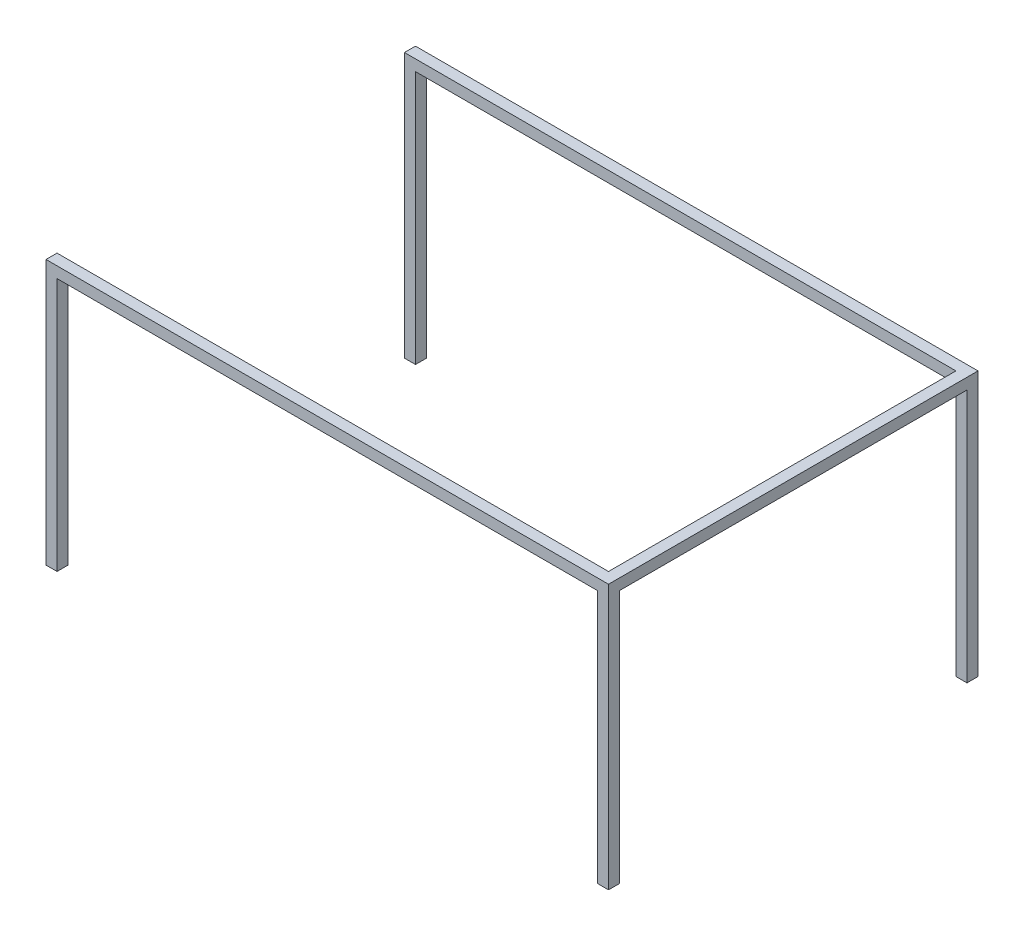
SolidWorks part; units mm, degrees
ref_plane "Front Plane" through (0, 0, 0) normal (0, 0, 1) x (1, 0, 0)
ref_plane "Top Plane" through (0, 0, 0) normal (0, 1, 0) x (1, 0, 0)
ref_plane "Right Plane" through (0, 0, 0) normal (1, 0, 0) x (0, 0, -1)
sketch "Sketch1" plane through (0, 0, 0) normal (0, 1, 0) x (1, 0, 0)
  line L0 (-55, 0) -> (55, 0) construction
  line L1 (-749.3, 400.05) -> (749.3, 400.05) construction
  line L2 (-749.3, 400.05) -> (-749.3, -400.05) construction
  line L3 (-749.3, -400.05) -> (749.3, -400.05) construction
  line L4 (749.3, 400.05) -> (749.3, -400.05) construction
  line L5 (-749.3, 400.05) -> (749.3, -400.05) construction
  line L6 (-749.3, -400.05) -> (749.3, 400.05) construction
  line L7 (749.3, -400.05) -> (-520.7, -400.05)
  line L8 (749.3, -400.05) -> (749.3, -425.45)
  line L9 (749.3, -425.45) -> (-520.7, -425.45)
  line L10 (-520.7, -400.05) -> (-520.7, -425.45)
  line L11 (749.3, 425.45) -> (-520.7, 425.45)
  line L12 (-520.7, 400.05) -> (-520.7, 425.45)
  line L13 (749.3, 400.05) -> (-520.7, 400.05)
  line L14 (749.3, 400.05) -> (749.3, 425.45)
  line L15 (749.3, 425.45) -> (749.3, -425.45)
  line L16 (749.3, 425.45) -> (774.7, 425.45)
  line L17 (749.3, -425.45) -> (774.7, -425.45)
  line L18 (774.7, 425.45) -> (774.7, -425.45)
  point P0 (0, 0)
extrude "Boss-Extrude1" add sketch "Sketch1" along normal blind 25.4 contours L7 L10 L9 L8 | L18 L16 L14 L15 L8 L17 | L11 L12 L13 L14 region at (114.3, 0, 412.75) region at (762, 0, 0)
sketch "Sketch2" plane through (0, 0, 0) normal (0, 1, 0) x (1, 0, 0)
  line L0 (749.3, 400.05) -> (-520.7, 400.05) construction
  line L1 (-520.7, 425.45) -> (-495.3, 425.45)
  line L2 (-520.7, 425.45) -> (-520.7, 400.05)
  line L3 (-520.7, 400.05) -> (-495.3, 400.05)
  line L4 (-495.3, 425.45) -> (-495.3, 400.05)
  line L5 (-55, 0) -> (55, 0) construction
  line L6 (774.7, 425.45) -> (749.3, 425.45)
  line L7 (774.7, 425.45) -> (774.7, 400.05)
  line L8 (774.7, 400.05) -> (749.3, 400.05)
  line L9 (749.3, 425.45) -> (749.3, 400.05)
  line L10 (749.3, -425.45) -> (749.3, -400.05)
  line L11 (774.7, -400.05) -> (749.3, -400.05)
  line L12 (774.7, -425.45) -> (774.7, -400.05)
  line L13 (774.7, -425.45) -> (749.3, -425.45)
  line L14 (-495.3, -425.45) -> (-495.3, -400.05)
  line L15 (-520.7, -400.05) -> (-495.3, -400.05)
  line L16 (-520.7, -425.45) -> (-520.7, -400.05)
  line L17 (-520.7, -425.45) -> (-495.3, -425.45)
extrude "Boss-Extrude2" add sketch "Sketch2" against normal blind 584.2
